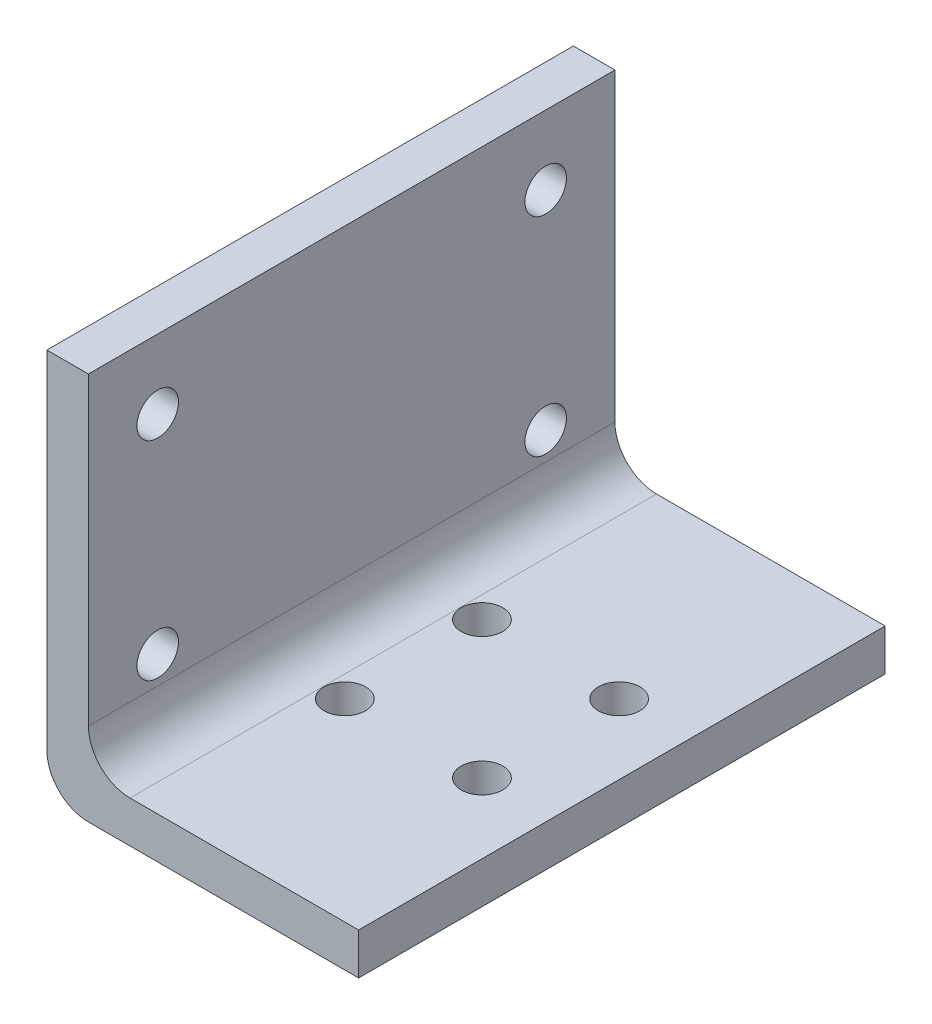
SolidWorks part; units mm, degrees
ref_plane "前视基准面" through (0, 0, 0) normal (0, 0, 1) x (1, 0, 0)
ref_plane "上视基准面" through (0, 0, 0) normal (0, 1, 0) x (1, 0, 0)
ref_plane "右视基准面" through (0, 0, 0) normal (1, 0, 0) x (0, 0, -1)
other "Configuration Table"
sketch "草图1" plane through (0, 0, 0) normal (0, 1, 0) x (1, 0, 0)
  line L1 (11.25, -19) -> (-11.25, -19)
  line L2 (11.25, -19) -> (11.25, 19)
  line L3 (11.25, 19) -> (-11.25, 19)
  line L4 (-11.25, -19) -> (-11.25, 19)
  line L5 (11.25, -19) -> (-11.25, 19) construction
  line L6 (11.25, 19) -> (-11.25, -19) construction
  point P0 (0, 0)
  dimension "D1" = 22.5
  dimension "D2" = 38
extrude "凸台-拉伸1" add sketch "草图1" along normal blind 3
sketch "草图2" plane through (0, 3, 0) normal (0, 1, 0) x (1, 0, 0)
  line L0 (-11.25, -19) -> (11.25, -19) construction
  line L1 (-11.25, 19) -> (-8.25, 19)
  line L2 (-11.25, 19) -> (-11.25, -19)
  line L3 (-11.25, -19) -> (-8.25, -19)
  line L4 (-8.25, 19) -> (-8.25, -19)
  dimension "D1" = 3
extrude "凸台-拉伸2" add sketch "草图2" along normal blind 25
sketch "草图3" plane through (0, 0, 0) normal (0, -1, 0) x (1, 0, 0)
  circle A0 centre (-3.6997, 5.0497) radius 1.5
  circle A1 centre (6.1997, 5.0497) radius 1.5
  circle A2 centre (-3.6997, -4.8497) radius 1.5
  circle A3 centre (6.1997, -4.8497) radius 1.5
extrude "切除-拉伸2" cut sketch "草图3" against normal blind 25
sketch "草图4" plane through (-8.25, 0, 0) normal (1, 0, 0) x (0, 0, -1)
  line L0 (19, 28) -> (19, 3) construction
  line L1 (-19, 28) -> (19, 28) construction
  line L2 (-19, 3) -> (19, 3) construction
  line L3 (-19, 28) -> (-19, 3) construction
  circle A0 centre (14, 23) radius 1.5
  circle A1 centre (-14, 23) radius 1.5
  circle A2 centre (-14, 8) radius 1.5
  circle A3 centre (14, 8) radius 1.5
  dimension "D1" = 3
  dimension "D4" = 5
  dimension "D2" = 5
  dimension "D3" = 5
  dimension "D5" = 5
  dimension "D6" = 5
  dimension "D7" = 5
  dimension "D8" = 5
  dimension "D9" = 5
extrude "切除-拉伸3" cut sketch "草图4" against normal blind 25
fillet "圆角1" radius 3 1 edges at (-8.25, 3, 0)
fillet "圆角2" radius 3 1 edges at (-11.25, 0, 0)
